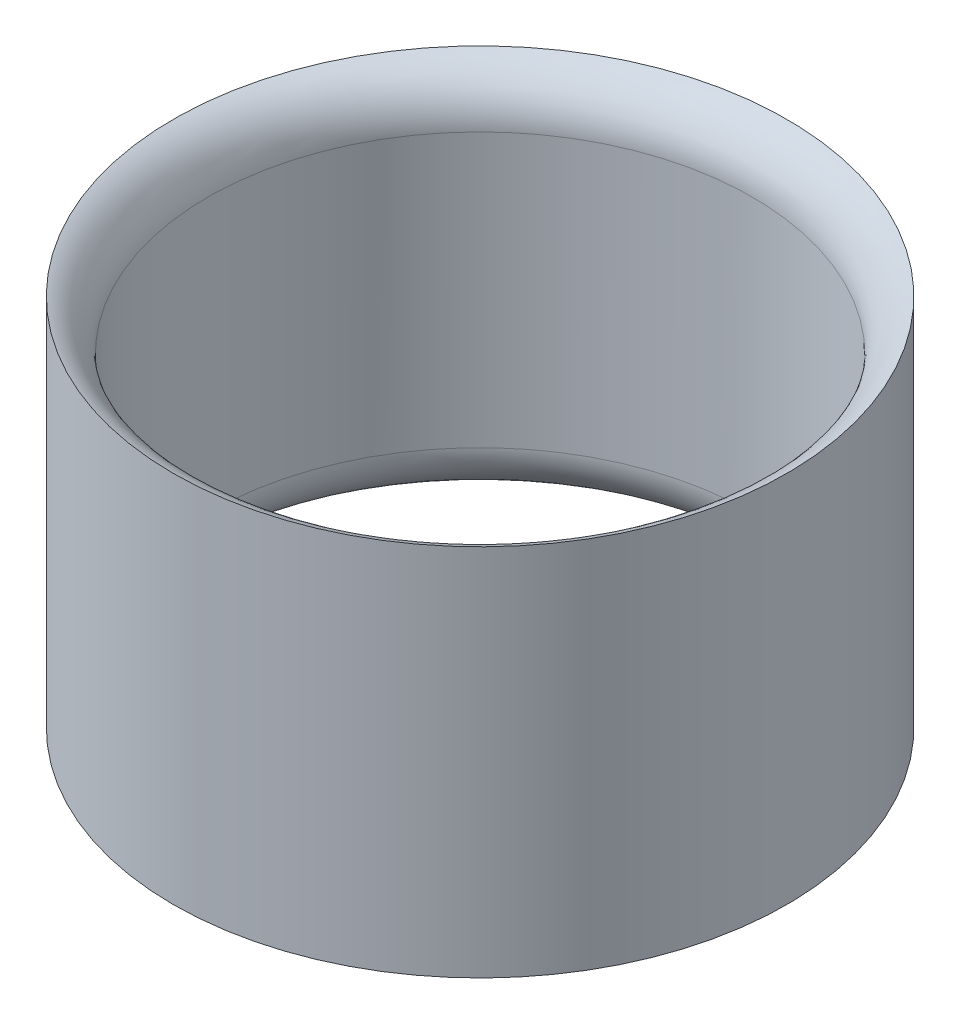
SolidWorks part; units mm, degrees
ref_plane "Front Plane" through (0, 0, 0) normal (0, 0, 1) x (1, 0, 0)
ref_plane "Top Plane" through (0, 0, 0) normal (0, 1, 0) x (1, 0, 0)
ref_plane "Right Plane" through (0, 0, 0) normal (1, 0, 0) x (0, 0, -1)
sketch "Sketch1" plane through (0, 0, 0) normal (0, 1, 0) x (1, 0, 0)
  circle A0 centre (0, 0) radius 14.605
  dimension "D1" = 29.21
extrude "Boss-Extrude1" add sketch "Sketch1" along normal blind 17.78
sketch "Sketch2" plane through (0, 17.78, 0) normal (0, 1, 0) x (1, 0, 0)
  circle A0 centre (0, 0) radius 12.954
  dimension "D1" = 25.908
extrude "Cut-Extrude1" cut sketch "Sketch2" against normal through all
fillet "Fillet1" radius 2.54 2 edges at (0, 0, 12.954) (0, 17.78, 12.954)
